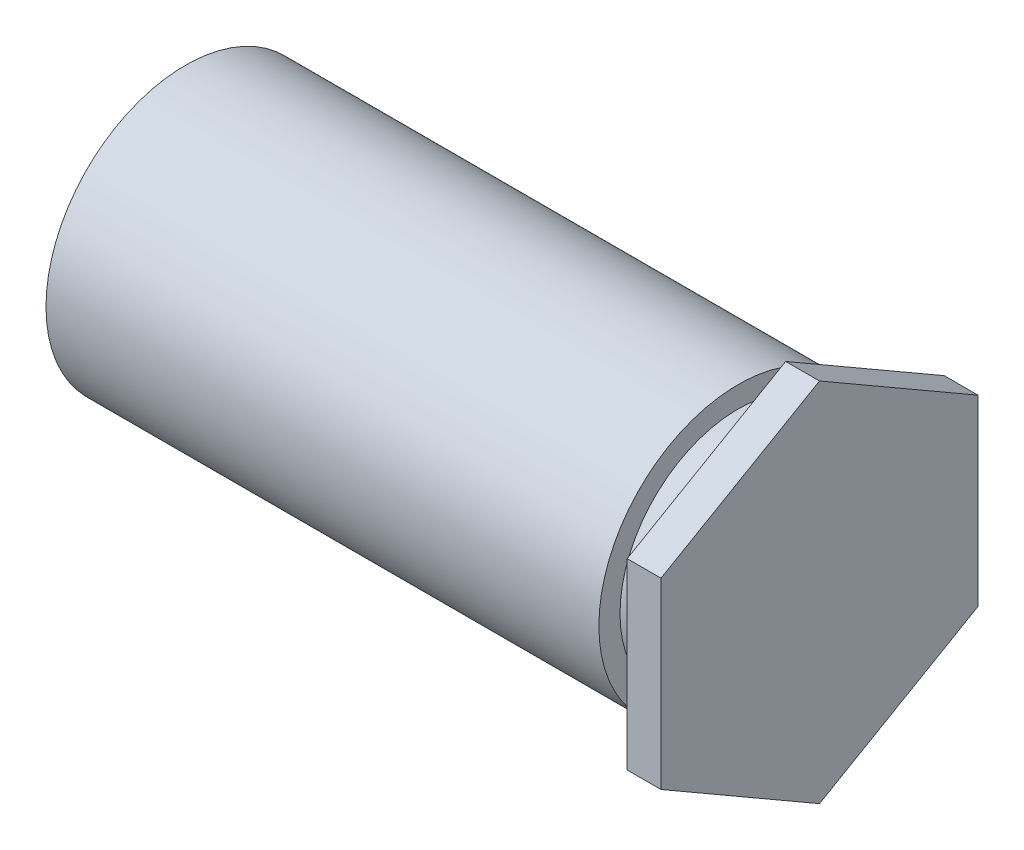
SolidWorks part; units mm, degrees
ref_plane "Front Plane" through (0, 0, 0) normal (0, 0, 1) x (1, 0, 0)
ref_plane "Top Plane" through (0, 0, 0) normal (0, 1, 0) x (1, 0, 0)
ref_plane "Right Plane" through (0, 0, 0) normal (1, 0, 0) x (0, 0, -1)
sketch "Sketch1" plane through (0, 0, 0) normal (0, 0, 1) x (1, 0, 0)
  line L0 (-4.7625, 0) -> (4.7625, 0) construction
  line L1 (-4.7625, 2.0955) -> (-4.7625, -2.0955) construction
  line L2 (-0.7938, 1.4224) -> (-0.7938, -1.4224) construction
  line L3 (4.7625, 2.3813) -> (4.7625, -2.3813) construction
  line L4 (-0.7938, 1.4224) -> (-4.7625, 1.4224) construction
  line L5 (-0.7938, -1.4224) -> (-4.7625, -1.4224) construction
  point P4 (-0.7938, 0)
  point P10 (4.2545, 0)
  point P11 (3.5433, 0)
  dimension "OD" = 4.191
  dimension "Length" = 9.525
  dimension "Thread Height" = 3.9688
  dimension "Thread Size" = 2.8448
  dimension "D1" = 4.7625
  dimension "D3" = 0.7112
  dimension "D4" = 0.508
ref_plane "Plane1" through (-4.7625, 0, 0) normal (1, 0, 0) x (0, 0, -1)
sketch "Sketch2" plane through (-4.7625, 0, 0) normal (1, 0, 0) x (0, 0, -1)
  circle A0 centre (0, 0) radius 2.0955
extrude "Extrude1" add sketch "Sketch2" along normal up to vertex (9.525 mm away) up to point (4.7625, 0, 0)
sketch "Sketch3" plane through (4.7625, 0, 0) normal (1, 0, 0) x (0, 0, -1)
  line L1 (0, 2.7496) -> (-2.3813, 1.3748)
  line L2 (-2.3813, 1.3748) -> (-2.3813, -1.3748)
  line L3 (-2.3813, -1.3748) -> (0, -2.7496)
  line L4 (0, -2.7496) -> (2.3813, -1.3748)
  line L5 (2.3813, -1.3748) -> (2.3813, 1.3748)
  line L6 (2.3813, 1.3748) -> (0, 2.7496)
  circle A0 centre (0, 0) radius 2.3813 construction
extrude "Extrude2" add sketch "Sketch3" against normal up to vertex (0.508 mm away) up to point (4.2545, 0, 0)
sketch "Sketch4" plane through (4.2545, 0, 0) normal (-1, 0, 0) x (0, 0, 1)
  circle A0 centre (0, 0) radius 1.778
  circle A1 centre (0, 0) radius 2.0955 construction
  circle A2 centre (0, 0) radius 2.0955
  dimension "D1" = 0.3175
extrude "Extrude3" cut sketch "Sketch4" along normal up to vertex (0.7112 mm away) up to point (3.5433, 0, 0)
sketch "Sketch5" plane through (-4.7625, 0, 0) normal (-1, 0, 0) x (0, 0, 1)
  line L0 (0, 0) -> (-1.0058, 1.0058) construction
  line L1 (0, 0) -> (-1.4224, 0) construction
  circle A0 centre (0, 0) radius 1.4224
  dimension "D1" = 45
extrude "Extrude4" cut sketch "Sketch5" against normal up to vertex (3.9688 mm away) up to point (-0.7938, 0, 0)
sketch "Sketch6" plane through (-4.7625, 0, 0) normal (-1, 0, 0) x (0, 0, 1)
  circle A1 centre (0, 0) radius 1.4224
  circle A2 centre (0, 0) radius 1.4224
  dimension "D1" = 0
curve "Helix/Spiral1" pitch 0.635 height 3.9688 turns 6.25 parameters "Pitch"=0.635
sketch "Sketch7" plane through (0, 0, 0) normal (0, 0, 1) x (1, 0, 0)
  line L0 (-5.3181, 1.4224) -> (-4.7625, 1.4224)
  line L1 (-5.3181, 1.4224) -> (-5.08, 1.01)
  line L2 (-5.08, 1.01) -> (-5.0006, 1.01)
  line L3 (-5.0006, 1.01) -> (-4.7625, 1.4224)
  line L4 (-5.0403, 1.01) -> (-5.0403, 1.4224) construction
  line L5 (-5.1991, 1.2162) -> (-4.8816, 1.2162) construction
  dimension "D1" = 60
  dimension "D2" = 0.0794
sweep "Sweep1" add profiles "Sketch7" path "Helix/Spiral1"
sketch "Sketch8" plane through (-4.7625, 0, 0) normal (-1, 0, 0) x (0, 0, 1)
  circle A2 centre (0, 0) radius 1.4732
  circle A3 centre (0, 0) radius 1.4732
  dimension "D1" = 0.0508
extrude "Extrude6" cut sketch "Sketch8" along normal through all and the other way through all draft 45
equation "\"D2@Sketch7\" = \"Pitch@Helix/Spiral1\"*.125"
equation "\"D3@Sketch7\" = \"Pitch@Helix/Spiral1\"*.5"
equation "\"D3@Helix/Spiral1\" = \"Thread Height@Sketch1\""
